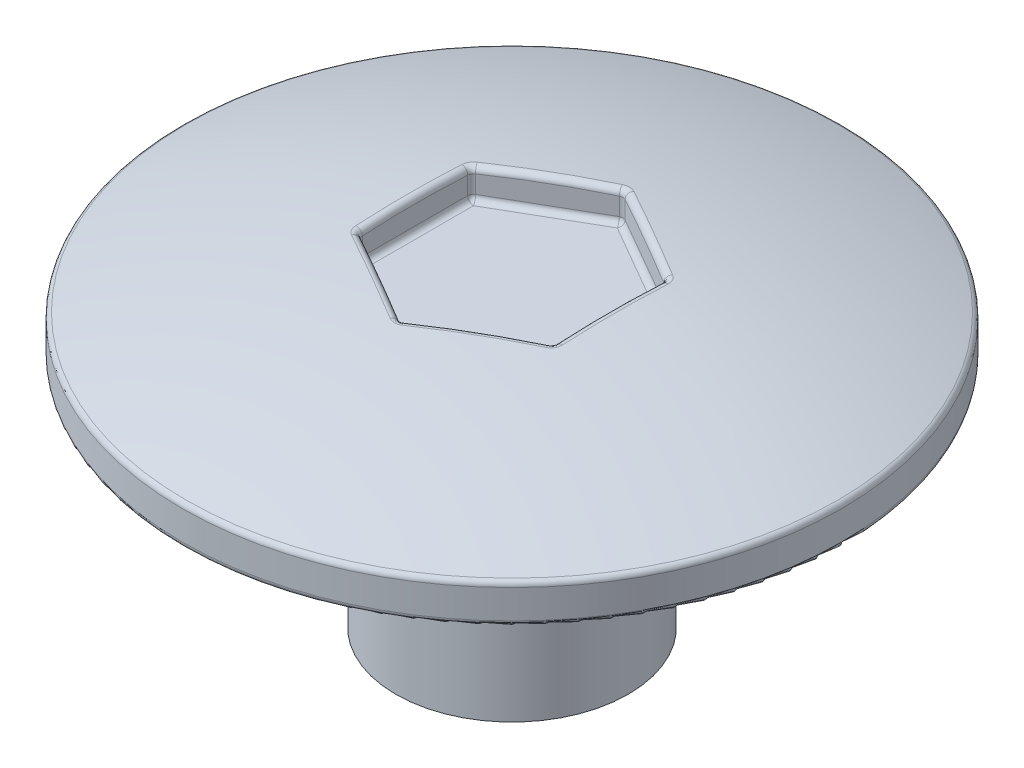
SolidWorks part; units mm, degrees
material "Cast Alloy Steel"
ref_plane "Front Plane" through (0, 0, 0) normal (0, 0, 1) x (1, 0, 0)
ref_plane "Top Plane" through (0, 0, 0) normal (0, 1, 0) x (1, 0, 0)
ref_plane "Right Plane" through (0, 0, 0) normal (1, 0, 0) x (0, 0, -1)
sketch "Sketch2" plane through (0, 0, 0) normal (0, 1, 0) x (1, 0, 0)
  circle A0 centre (0, 0) radius 8.5
extrude "Extrude1" add sketch "Sketch2" along normal blind 1
dome "Dome1" faces to dome 1 distance 1.5 reverse direction no elliptical dome no face at (0, 1, 8.5) parameters "D1"=1.5
ref_plane "Plane1" through (0, 3.0621, 0) normal (0, 1, 0) x (-1, 0, 0)
sketch "Sketch3" plane through (0, 3.0621, 0) normal (0, 1, 0) x (-1, 0, 0)
  line L1 (0, 2.8868) -> (-2.5, 1.4434)
  line L2 (-2.5, 1.4434) -> (-2.5, -1.4434)
  line L3 (-2.5, -1.4434) -> (0, -2.8868)
  line L4 (0, -2.8868) -> (2.5, -1.4434)
  line L5 (2.5, -1.4434) -> (2.5, 1.4434)
  line L6 (2.5, 1.4434) -> (0, 2.8868)
  circle A0 centre (0, 0) radius 2.5 construction
extrude "Extrude2" cut sketch "Sketch3" against normal blind 1.5
fillet "Fillet1" radius 0.15 18 edges at (-1.25, 2.3738, 2.1651) (1.25, 1.5621, -2.1651) (1.25, 2.3738, -2.1651) (0, 1.9469, -2.8868) (-1.25, 1.5621, -2.1651) (-1.25, 2.3738, -2.1651) (-2.5, 1.9469, -1.4434) (-2.5, 1.5621, 0) (-2.5, 1.9469, 1.4434) (-2.5, 2.3738, 0) (0, 1.9469, 2.8868) (1.25, 1.5621, 2.1651) (1.25, 2.3738, 2.1651) (2.5, 1.9469, 1.4434) (2.5, 1.5621, 0) (2.5, 1.9469, -1.4434) (2.5, 2.3738, 0) (-1.25, 1.5621, 2.1651)
fillet "Fillet2" radius 0.15 2 edges at (0, 0, 8.5) (0, 1, 8.5)
sketch "Sketch4" plane through (0, 0, 0) normal (0, -1, 0) x (1, 0, 0)
  circle A0 centre (0, 0) radius 3
extrude "Extrude3" add sketch "Sketch4" along normal blind 6
